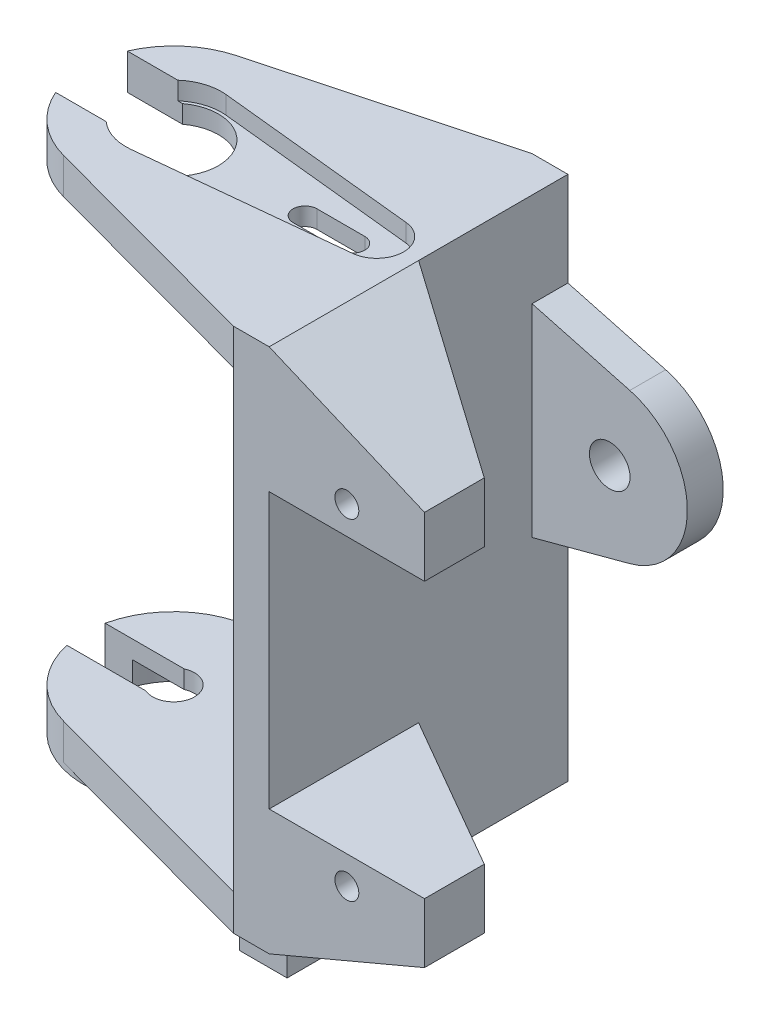
SolidWorks part; units mm, degrees
ref_plane "Plano frontal" through (0, 0, 0) normal (0, 0, 1) x (1, 0, 0)
ref_plane "Plano superior" through (0, 0, 0) normal (0, 1, 0) x (1, 0, 0)
ref_plane "Plano direito" through (0, 0, 0) normal (1, 0, 0) x (0, 0, -1)
sketch "Esboço1" plane through (0, 0, 0) normal (0, 0, 1) x (1, 0, 0)
  line L1 (0, -22) -> (-33, -22)
  line L2 (-33, -22) -> (-33, -19)
  line L3 (-33, -19) -> (-3, -19)
  line L4 (-3, -19) -> (-3, 19)
  line L5 (-3, 19) -> (-33, 19)
  line L6 (-33, 19) -> (-33, 22)
  line L7 (-33, 22) -> (0, 22)
  line L8 (0, 22) -> (13, 16.5)
  line L9 (13, 16.5) -> (13, 11.5)
  line L10 (13, 11.5) -> (0, 11.5)
  line L11 (0, -22) -> (13, -16.5)
  line L12 (13, -16.5) -> (13, -11.5)
  line L13 (13, -11.5) -> (0, -11.5)
  line L14 (0, 11.5) -> (0, -11.5)
  line L17 (0, 0) -> (31.9596, 0) construction
  circle A0 centre (6.5, 13.85) radius 1
  circle A2 centre (6.5, -13.85) radius 1
  point P4 (0, 0)
  point P19 (0, 0)
  point P20 (-3, 0)
  point P23 (6.5, 11.5)
  dimension "D9" = 2
  dimension "D1" = 23
  dimension "D2" = 3
  dimension "D3" = 13
  dimension "D4" = 5
  dimension "D5" = 3
  dimension "D6" = 38
  dimension "D7" = 30
  dimension "D10" = 27.7
extrude "Ressalto-extrusão1" add sketch "Esboço1" along normal mid plane 25
sketch "Esboço2" plane through (0, 22, 0) normal (0, 1, 0) x (1, 0, 0)
  line L0 (-33, -12.5) -> (-33, 12.5) construction
  line L1 (-20.5, 0) -> (-33, 0) construction
  line L2 (0, 0) -> (-3.8141, 0) construction
  line L3 (-3, 12.5) -> (-22.4572, 7.2401)
  line L4 (-22.75, 3) -> (-27.3739, 3)
  line L5 (-22.75, -3) -> (-27.3739, -3)
  line L6 (13, 12.5) -> (0, 12.5) construction
  line L7 (-3, 12.5) -> (-3, -12.5) construction
  line L8 (13, -12.5) -> (0, -12.5) construction
  line L9 (-3, -12.5) -> (-22.4572, -7.2401)
  line L10 (-3, 12.5) -> (-33, 12.5)
  line L11 (-33, 12.5) -> (-33, -12.5)
  line L12 (-33, -12.5) -> (-3, -12.5)
  line L13 (-33, -12.5) -> (-33, 12.5) construction
  line L14 (-20.5, 3) -> (-33, 3) construction
  line L15 (-20.5, -3) -> (-33, -3) construction
  line L16 (-9.5, 1) -> (-5.5, 1)
  line L17 (-9.5, -1) -> (-5.5, -1)
  arc A0 (-22.75, -3) -> (-22.75, 3) centre (-20.5, 0) ccw
  arc A1 (-5.5, -1) -> (-5.5, 1) centre (-5.5, 0) ccw
  arc A2 (-22.4572, 7.2401) -> (-27.3739, -3) centre (-20.5, 0) ccw
  arc A3 (-27.3739, -3) -> (-22.4572, -7.2401) centre (-20.5, 0) ccw
  arc A4 (-9.5, 1) -> (-9.5, -1) centre (-9.5, 0) ccw
  point P10 (-33, 0)
  line M3 (0, 12.5) -> (-33, 12.5)
  line M4 (-33, 12.5) -> (-33, -12.5)
  line M5 (-33, -12.5) -> (0, -12.5)
  dimension "D1" = 7.5
  dimension "D3" = 2
  dimension "D2" = 15
  dimension "D5" = 15
  dimension "D4" = 12.5
  dimension "D6" = 16
  dimension "D9" = 4
  dimension "D7" = 3
  dimension "D8" = 3
extrude "Corte-extrusão1" cut sketch "Esboço2" against normal blind 15 contours A3 A2 L3 L9 M3 M4 M5 | L4 A2 L5 A0 | A1 region at (-12.8305, 22, -10.247) region at (-22.3569, 22, 0) region at (-7.5, 22, 0)
sketch "Esboço4" plane through (0, -11.5, 0) normal (0, 1, 0) x (1, 0, 0)
  line L0 (13, -12.5) -> (13, 12.5) construction
  line L1 (13, -7.5) -> (0, 0.0056)
  line L2 (13, -7.5) -> (13, 12.5)
  line L3 (13, 12.5) -> (0, 12.5)
  line L4 (0, 0.0056) -> (0, 12.5)
  line L6 (0, -12.5) -> (0, 12.5) construction
  dimension "D1" = 5
  dimension "D2" = 60
extrude "Corte-extrusão2" cut sketch "Esboço4" against normal through all both and the other way through all
sketch "Esboço5" plane through (0, 0, -12.5) normal (0, 0, -1) x (-1, 0, 0)
  line L0 (-6.5, 13.85) -> (-6.5, -13.85) construction
  line L1 (-8.1823, 11.9285) -> (0, 14.121)
  line L2 (0, -11.5) -> (0, 11.5) construction
  line L3 (-8.1823, -0.6285) -> (0, -2.821)
  line L4 (0, 14.121) -> (0, -2.821)
  line L7 (-13, 11.5) -> (-13, 16.5) construction
  arc A0 (-8.1823, 11.9285) -> (-8.1823, -0.6285) centre (-6.5, 5.65) ccw
  circle A1 centre (-6.5, 5.65) radius 1.7
  point P16 (-6.5, 0)
  dimension "D1" = 3.4
  dimension "D3" = 5.65
  dimension "D2" = 75
extrude "Ressalto-extrusão2" add sketch "Esboço5" against normal blind 3
sketch "Esboço7" plane through (0, -19, 0) normal (0, 1, 0) x (1, 0, 0)
  line L0 (-20.5, 0) -> (-33, 0) construction
  line L1 (-21.2089, 1.6) -> (-33, 1.6)
  line L2 (-21.2089, -1.6) -> (-33, -1.6)
  line L3 (-20.5, -1.6) -> (-33, -1.6) construction
  line L4 (-20.5, 1.6) -> (-33, 1.6) construction
  line L5 (-33, -12.5) -> (-33, 12.5) construction
  line L6 (-33, 1.6) -> (-33, -1.6)
  arc A0 (-21.2089, -1.6) -> (-21.2089, 1.6) centre (-20.5, 0) ccw
  dimension "D1" = 3.5
  dimension "D2" = 1.6
  dimension "D3" = 1.6
extrude "Corte-extrusão3" cut sketch "Esboço7" against normal blind 10
extrude "Corte-extrusão4" cut sketch "Esboço2<2>" against normal through all contours M4 | A3 A2 L3 L9 M3 M4 M5 region at (-12.8305, 22, -10.247)
sketch "Esboço2<2>" plane through (0, 22, 0) normal (0, 1, 0) x (1, 0, 0) same geometry as "Esboço2"
sketch "Esboço8" plane through (0, 0, 0) normal (1, 0, 0) x (0, 0, -1)
  line L0 (0, 0) -> (0, -11.3279) construction
  line L2 (-1.6213, -28.5) -> (-1.6213, -25.5) construction
  line L3 (1.7574, -25.5) -> (3.8787, -27.6213) construction
  line L4 (10, -21.5) -> (3, -28.5)
  line L5 (3, -28.5) -> (-7, -28.5)
  line L6 (-7, -28.5) -> (-7, -25.5)
  line L7 (-7, -25.5) -> (-5, -24)
  line L8 (-5, -24) -> (-5, -25.5)
  line L9 (-5, -25.5) -> (1.7574, -25.5)
  line L10 (12.5, 0) -> (-12.5, 0) construction
  line L11 (12.5, 19) -> (12.5, -19) construction
  line L12 (-12.5, 19) -> (-12.5, -19) construction
  line L13 (1.7574, -25.5) -> (5.7574, -21.5)
  line L24 (5.7574, -21.5) -> (10, -21.5)
extrude "Ressalto-extrusão3" add sketch "Esboço8" against normal blind 4 from offset 4 offset against normal yes
sketch "Esboço9" plane through (0, -22, 0) normal (0, -1, 0) x (-1, 0, 0)
  circle A0 centre (20.5, 0) radius 5.3
  arc A2 (27.8273, 1.6) -> (22.4572, 7.2401) centre (20.5, 0) ccw construction
  dimension "D1" = 10.6
extrude "Corte-extrusão5" cut sketch "Esboço9" against normal blind 1.5
sketch "Esboço10" plane through (0, -22, 0) normal (0, -1, 0) x (1, 0, 0)
  line L8 (-22.4572, -7.2401) -> (-3, -12.5)
  line L9 (-3, 12.5) -> (-22.4572, 7.2401)
  line L10 (-27.8273, 1.6) -> (-25.5527, 1.6)
  line L11 (-3, -12.5) -> (0, -12.5)
  line L12 (0, -12.5) -> (0, -0.0056)
  line L13 (0, -0.0056) -> (0, 12.5)
  line L14 (0, 12.5) -> (-3, 12.5)
  line L15 (-27.8273, 1.6) -> (-25.5527, 1.6)
  line L16 (-25.5527, -1.6) -> (-27.8273, -1.6)
  line L17 (-25.5527, -1.6) -> (-27.8273, -1.6)
  arc A1 (-27.8273, -1.6) -> (-22.4572, -7.2401) centre (-20.5, 0) ccw
  arc A2 (-22.4572, 7.2401) -> (-27.8273, 1.6) centre (-20.5, 0) ccw
  arc A5 (-27.8273, -1.6) -> (-27.8273, 1.6) centre (-20.5, 0) ccw
  arc A6 (-25.5527, -1.6) -> (-25.5527, 1.6) centre (-20.5, 0) ccw
  arc A7 (-25.5527, -1.6) -> (-25.5527, 1.6) centre (-20.5, 0) ccw
  dimension "D1" = 0
extrude "Ressalto-extrusão4" add sketch "Esboço10" along normal blind 0.5
sketch "Esboço11" plane through (0, 22, 0) normal (0, 1, 0) x (1, 0, 0)
  line L0 (-20.0882, 3.9787) -> (-3.2684, 2.238)
  line L1 (-20.0882, -3.9787) -> (-3.2684, -2.238)
  arc A0 (-20.0882, 3.9787) -> (-20.0882, -3.9787) centre (-20.5, 0) ccw
  arc A1 (-3.2684, -2.238) -> (-3.2684, 2.238) centre (-3.5, 0) ccw
  point P9 (-20.0625, -3.976)
  dimension "D1" = 8
  dimension "D2" = 4.5
  dimension "D3" = 17
extrude "Corte-extrusão6" cut sketch "Esboço11" against normal blind 1.5
